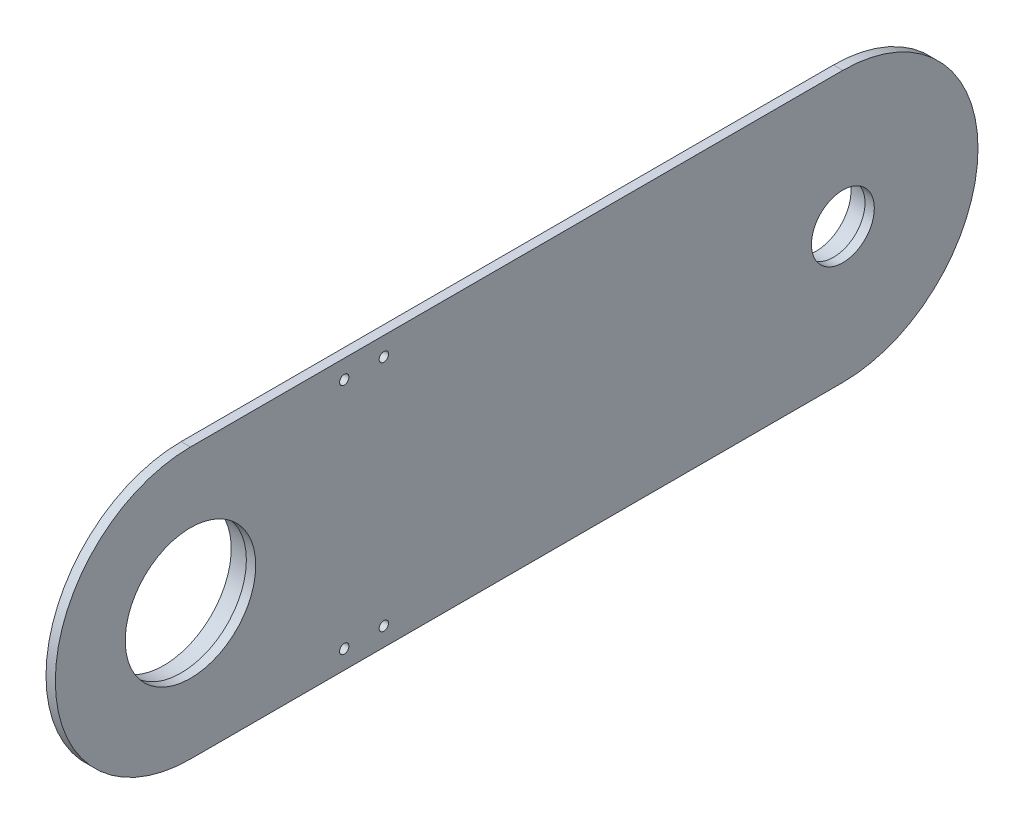
SolidWorks part; units mm, degrees
ref_plane "Front Plane" through (0, 0, 0) normal (0, 0, 1) x (1, 0, 0)
ref_plane "Top Plane" through (0, 0, 0) normal (0, 1, 0) x (1, 0, 0)
ref_plane "Right Plane" through (0, 0, 0) normal (1, 0, 0) x (0, 0, -1)
sketch "Sketch1" plane through (0, 0, 0) normal (1, 0, 0) x (0, 0, -1)
  line L0 (0, 0) -> (280, 0) construction
  line L1 (0, 58) -> (280, 58)
  line L2 (0, -58) -> (280, -58)
  arc A0 (0, 58) -> (0, -58) centre (0, 0) ccw
  arc A1 (280, -58) -> (280, 58) centre (280, 0) ccw
  circle A2 centre (0, 0) radius 28
  circle A3 centre (280, 0) radius 13.5
  point P3 (140, 0)
  dimension "D2" = 58
  dimension "D3" = 56
  dimension "D4" = 27
  dimension "D1" = 280
extrude "Boss-Extrude1" add sketch "Sketch1" along normal blind 4
ref_plane "Plane1" through (-7.5, 0, 0) normal (-1, 0, 0) x (0, 0, 1)
sketch "Sketch2" plane through (-7.5, 0, 0) normal (-1, 0, 0) x (0, 0, 1)
  line L0 (-140, 58) -> (-140, -58) construction
  line L1 (-280, 58) -> (0, 58) construction
  line L2 (0, -58) -> (-280, -58) construction
  circle A0 centre (0, 0) radius 29
  circle A1 centre (0, 0) radius 35
  circle A2 centre (-280, 0) radius 15
  circle A3 centre (-280, 0) radius 20
  dimension "D1" = 58
  dimension "D2" = 70
  dimension "D3" = 30
  dimension "D4" = 40
extrude "Boss-Extrude2" add sketch "Sketch2" against normal up to surface (7.5 mm away) up to face at (0, 0, -140)
chamfer "Chamfer1" distance 8 angle 45 2 edges at (0, 0, -35) (0, 0, -300)
sketch "Sketch3" plane through (0, 0, 0) normal (-1, 0, 0) x (0, 0, 1)
  line L0 (0, 58) -> (-73, 58) construction
  line L1 (-280, 58) -> (0, 58) construction
  line L2 (-73, 58) -> (-73, -58) construction
  line L3 (0, -58) -> (-280, -58) construction
  line L4 (-73, 58) -> (-76, 58) construction
  line L5 (-76, 58) -> (-76, -58) construction
  line L6 (-69.0931, 53.5) -> (-66, 53.5) construction
  line L7 (-66, 46.5) -> (-69.0931, 46.5) construction
  line L8 (-66, 50) -> (-73, 50) construction
  line L9 (-73, 55.8533) -> (-73, 44.1467) construction
  line L10 (-73, 0) -> (-99.886, 0) construction
  line L11 (-74.5, 58) -> (-74.5, 37.4458) construction
  arc A0 (-69.0931, 53.5) -> (-73, 55.8533) centre (-69.0931, 57.9197) cw construction
  arc A1 (-66, 53.5) -> (-66, 46.5) centre (-66, 50) cw construction
  arc A2 (-69.0931, 46.5) -> (-73, 44.1467) centre (-69.0931, 42.0803) ccw construction
  circle A3 centre (-66, 50) radius 2
  circle A4 centre (-66, -50) radius 2
  circle A5 centre (-83, -50) radius 2
  circle A6 centre (-83, 50) radius 2
  dimension "D3" = 4
  dimension "D1" = 73
  dimension "D2" = 3
  dimension "D4" = 7
  dimension "D5" = 8
  dimension "D6" = 7
extrude "Cut-Extrude1" cut sketch "Sketch3" against normal through all contours A3 | A4 | A6 | A5
equation "\"mini-flipper-shaft-diameter\"= 26mm"
equation "\"mini-shaft-ring-groove-diam\"= 7.8mm"
equation "\"mini-shaft-ring-groove-width\"= 1mm"
equation "\"dtCoverPlate-DistFrom-GearCent\" = 73mm"
equation "\"wormGearShaft-L\" = \"dtCoverPlate-DistFrom-GearCent\" - 27.75 + 3.75"
equation "\"D1@Sketch3\"=\"dtCoverPlate-DistFrom-GearCent\""
